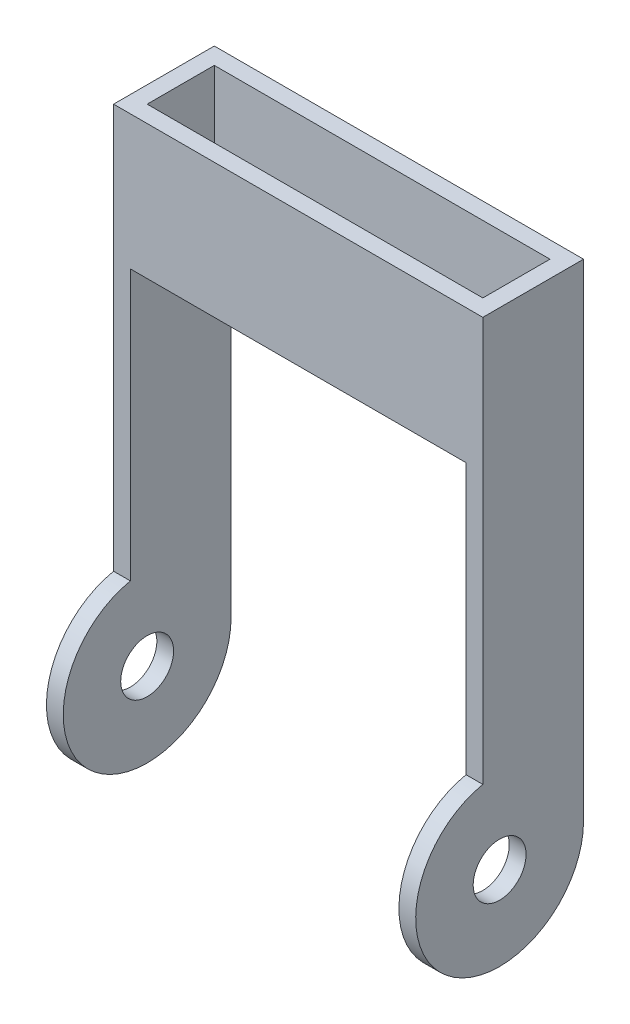
SolidWorks part; units mm, degrees
material "6061-T6 (SS)"
ref_plane "Front Plane" through (0, 0, 0) normal (0, 0, 1) x (1, 0, 0)
ref_plane "Top Plane" through (0, 0, 0) normal (0, 1, 0) x (1, 0, 0)
ref_plane "Right Plane" through (0, 0, 0) normal (1, 0, 0) x (0, 0, -1)
sketch "ProbeProfile" plane through (0, 0, 0) normal (0, 1, 0) x (1, 0, 0)
  line L1 (-31.75, -6.35) -> (31.75, -6.35)
  line L2 (-31.75, -6.35) -> (-31.75, 6.35)
  line L3 (-31.75, 6.35) -> (31.75, 6.35)
  line L4 (31.75, -6.35) -> (31.75, 6.35)
  line L5 (-31.75, -6.35) -> (31.75, 6.35) construction
  line L6 (-31.75, 6.35) -> (31.75, -6.35) construction
  point P0 (0, 0)
  dimension "D1" = 12.7
  dimension "D2" = 63.5
extrude "Extrude-Thin1" add sketch "ProbeProfile" along normal blind 25.4 thin thin type one direction wall 3.175
sketch "Sketch2" plane through (0, 0, 0) normal (1, 0, 0) x (0, 0, -1)
  line L1 (9.525, 25.4) -> (9.525, 0) construction
  line L2 (9.525, 0) -> (-9.525, 0) construction
  circle A0 centre (-6.35, -66.675) radius 15.875
  point P4 (9.525, -66.675)
  dimension "D1" = 31.75
  dimension "D2" = 66.675
extrude "Boss-Extrude1" add sketch "Sketch2" along normal mid plane 69.85 separate body
extrude "Cut-Extrude1" cut sketch "Sketch2<2>" against normal mid plane 63.5
sketch "Sketch2<2>" plane through (0, 0, 0) normal (1, 0, 0) x (0, 0, -1) same geometry as "Sketch2"
sketch "Sketch3" plane through (0, 0, 0) normal (0, -1, 0) x (1, 0, 0)
  line L0 (-34.925, 9.525) -> (34.925, 9.525) construction
  line L1 (34.925, -9.525) -> (31.75, -9.525)
  line L2 (34.925, -9.525) -> (34.925, 9.525)
  line L3 (34.925, 9.525) -> (31.75, 9.525)
  line L4 (31.75, -9.525) -> (31.75, 9.525)
  line L5 (-31.75, -6.35) -> (-31.75, 6.35) construction
  line L6 (-34.925, -9.525) -> (-31.75, -9.525)
  line L7 (-34.925, -9.525) -> (-34.925, 9.525)
  line L8 (-34.925, 9.525) -> (-31.75, 9.525)
  line L9 (-31.75, -9.525) -> (-31.75, 9.525)
  line L10 (31.75, 6.35) -> (31.75, -6.35) construction
extrude "Boss-Extrude2" add sketch "Sketch3" along normal up to surface (66.675 mm away) up to face at (-34.925, -66.675, -9.525)
sketch "Sketch4" plane through (-34.925, 0, 0) normal (-1, 0, 0) x (0, 0, 1)
  circle A0 centre (6.35, -66.675) radius 5.0038
  point P0 (6.35, -66.675)
  dimension "D1" = 10.0076
extrude "Cut-Extrude2" cut sketch "Sketch4" against normal up to surface (69.85 mm away)
